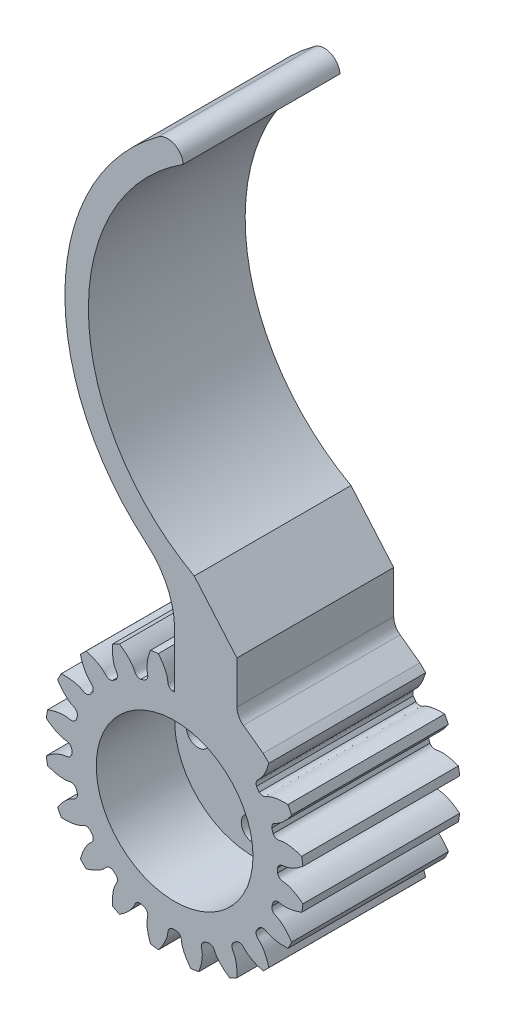
SolidWorks part; units mm, degrees
material "聚脂树脂"
ref_plane "前视基准面" through (0, 0, 0) normal (0, 0, 1) x (1, 0, 0)
ref_plane "上视基准面" through (0, 0, 0) normal (0, 1, 0) x (1, 0, 0)
ref_plane "右视基准面" through (0, 0, 0) normal (1, 0, 0) x (0, 0, -1)
other "Configuration Table"
sketch "草图1" plane through (0, 0, 0) normal (0, 0, 1) x (1, 0, 0)
  circle A0 centre (0, 0) radius 16.5
extrude "凸台-拉伸1" add sketch "草图1" along normal blind 20
ref_axis "基准轴1" through (0, 0, -1.5) along (0, 0, 1)
sketch "草图2" plane through (0, 0, 0) normal (0, 0, 1) x (1, 0, 0)
  line L0 (0, 0) -> (0, 16.5) construction
  circle A0 centre (0, 0) radius 16.5 construction
  arc A1 (0.29, 13.1218) -> (-0.29, 13.1218) centre (0, 0) ccw
  arc A2 (4.7717, 18.7474) -> (-4.7717, 18.7474) centre (0, 0) ccw
  spline S0 degree 3 poles (0.29, 13.1218) (0.9168, 13.3402) (0.8356, 13.7807) (0.9193, 14.205) (0.9283, 14.2463) (0.9395, 14.293) (0.9529, 14.3448) (0.969, 14.4018) (0.9878, 14.4638) (1.0095, 14.5309) (1.0345, 14.6028) (1.0629, 14.6795) (1.0948, 14.7608) (1.1305, 14.8467) (1.1702, 14.9371) (1.2141, 15.0317) (1.2623, 15.1305) (1.315, 15.2334) (1.3725, 15.3401) (1.4349, 15.4506) (1.5023, 15.5646) (1.575, 15.6821) (1.653, 15.8029) (1.7366, 15.9267) (1.826, 16.0534) (1.9211, 16.1829) (2.0223, 16.3149) (2.1296, 16.4493) (2.2432, 16.5859) (2.3632, 16.7244) (2.4897, 16.8646) (2.6229, 17.0065) (2.7628, 17.1496) (2.9095, 17.2939) (3.0632, 17.4391) (3.224, 17.585) (3.3918, 17.7313) (3.567, 17.8779) (3.7493, 18.0245) (3.9391, 18.1709) (4.1363, 18.3167) (4.4122, 18.5125) (4.6259, 18.6545) (4.7717, 18.7474) knots 0 0 0 0 0.165916 0.170906 0.176664 0.183189 0.190482 0.198542 0.207371 0.216967 0.22733 0.238462 0.250361 0.263027 0.276462 0.290664 0.305634 0.321371 0.337876 0.355149 0.37319 0.391998 0.411574 0.431917 0.453028 0.474907 0.497554 0.520968 0.54515 0.570099 0.595817 0.622302 0.649554 0.677575 0.706363 0.735918 0.766242 0.797333 0.829191 0.861818 0.895212 0.929373 1 1 1 1
  spline S1 degree 3 poles (-0.29, 13.1218) (-0.9168, 13.3402) (-0.8356, 13.7807) (-0.9193, 14.205) (-0.9283, 14.2463) (-0.9395, 14.293) (-0.9529, 14.3448) (-0.969, 14.4018) (-0.9878, 14.4638) (-1.0095, 14.5309) (-1.0345, 14.6028) (-1.0629, 14.6795) (-1.0948, 14.7608) (-1.1305, 14.8467) (-1.1702, 14.9371) (-1.2141, 15.0317) (-1.2623, 15.1305) (-1.315, 15.2334) (-1.3725, 15.3401) (-1.4349, 15.4506) (-1.5023, 15.5646) (-1.575, 15.6821) (-1.653, 15.8029) (-1.7366, 15.9267) (-1.826, 16.0534) (-1.9211, 16.1829) (-2.0223, 16.3149) (-2.1296, 16.4493) (-2.2432, 16.5859) (-2.3632, 16.7244) (-2.4897, 16.8646) (-2.6229, 17.0065) (-2.7628, 17.1496) (-2.9095, 17.2939) (-3.0632, 17.4391) (-3.224, 17.585) (-3.3918, 17.7313) (-3.567, 17.8779) (-3.7493, 18.0245) (-3.9391, 18.1709) (-4.1363, 18.3167) (-4.4122, 18.5125) (-4.6259, 18.6545) (-4.7717, 18.7474) knots 0 0 0 0 0.165916 0.170906 0.176664 0.183189 0.190482 0.198542 0.207371 0.216967 0.22733 0.238462 0.250361 0.263027 0.276462 0.290664 0.305634 0.321371 0.337876 0.355149 0.37319 0.391998 0.411574 0.431917 0.453028 0.474907 0.497554 0.520968 0.54515 0.570099 0.595817 0.622302 0.649554 0.677575 0.706363 0.735918 0.766242 0.797333 0.829191 0.861818 0.895212 0.929373 1 1 1 1
extrude "切除-拉伸1" cut sketch "草图2" along normal through all
pattern_circular "阵列(圆周)1" count 20 over 360 about axis through (0, 0, -1.5) along (0, 0, 1) of "切除-拉伸1"
sketch "草图3" plane through (0, 0, 0) normal (0, 0, 1) x (1, 0, 0)
  circle A0 centre (0, 0) radius 15 construction
  dimension "Dn" = 30
sketch "草图4" plane through (0, 0, 0) normal (0, 0, -1) x (-1, 0, 0)
  line L0 (0, 0) -> (67.6919, 0) construction
  line L1 (0, 13.125) -> (0, 76.7697) construction
  line L2 (-15, 0) -> (-15, 67.6903) construction
  line L3 (-7.9502, 14.4584) -> (-7.9502, 25)
  line L4 (0, 13.125) -> (0, 25.2067)
  line L5 (-2.1023, 76) -> (-1.1024, 72)
  line L6 (-7.9502, 14.4584) -> (-11.294, 12.029)
  circle A2 centre (-15, 50.026) radius 26 construction
  circle A3 centre (-15, 50.026) radius 29 construction
  arc A4 (-7.9502, 25) -> (-1.1024, 72) centre (-15, 50.026) ccw
  arc A5 (0, 25.2067) -> (-2.1023, 76) centre (-15, 50.026) ccw
  arc A6 (0.29, 13.1218) -> (-0.29, 13.1218) centre (0, 0) ccw construction
  arc A7 (-2.0665, 16.3701) -> (-3.0932, 16.2075) centre (0, 0) ccw construction
  arc A8 (-3.7791, 12.5692) -> (-4.3306, 12.39) centre (0, 0) ccw construction
  arc A9 (-7.024, 14.9303) -> (-7.9502, 14.4584) centre (0, 0) ccw construction
  arc A10 (0, 13.125) -> (-0.29, 13.1218) centre (0, 0) ccw
  arc A11 (-2.0665, 16.3701) -> (-3.0932, 16.2075) centre (0, 0) ccw
  arc A12 (-3.7791, 12.5692) -> (-4.3306, 12.39) centre (0, 0) ccw
  arc A13 (-7.024, 14.9303) -> (-7.9502, 14.4584) centre (0, 0) ccw
  arc A14 (-7.4782, 10.7862) -> (-7.9474, 10.4453) centre (0, 0) ccw construction
  arc A15 (-7.4782, 10.7862) -> (-7.9474, 10.4453) centre (0, 0) ccw
  spline S2 degree 3 poles (3856.7688, 1071.746) (-40.9447, -7.0022) (0.397, 7.533) (-0.9224, 14.2207) (-0.9359, 14.2793) (-0.9529, 14.3448) (-0.969, 14.4018) (-0.9951, 14.4881) (-1.0357, 14.6084) (-1.0961, 14.7664) (-1.1716, 14.9426) (-1.2638, 15.1361) (-1.3741, 15.3456) (-1.5041, 15.5702) (-1.6549, 15.8084) (-1.7965, 16.0133) (-1.9211, 16.1829) (-22.6396, 43.218) (-204.8238, -56.137) (3987.8439, 293.2807) knots -2.601051 -2.601051 -2.601051 -2.601051 0.165916 0.170906 0.183189 0.190482 0.198542 0.207371 0.22733 0.250361 0.276462 0.305634 0.337876 0.37319 0.411574 0.453028 0.474907 0.497554 14.365332 14.365332 14.365332 14.365332 only from (-0.29, 13.1218) to (-2.0665, 16.3701) construction
  spline S3 degree 3 poles (-3999.1929, -172.5161) (41.1045, 5.9931) (-2.7054, 7.0416) (-3.5171, 13.8097) (-3.5224, 13.8696) (-3.5265, 13.9372) (-3.5289, 13.9963) (-3.5307, 14.0865) (-3.5293, 14.2134) (-3.5206, 14.3824) (-3.5033, 14.5733) (-3.4754, 14.7858) (-3.4352, 15.0192) (-3.381, 15.2729) (-3.3111, 15.5461) (-3.2398, 15.7847) (-3.1737, 15.9845) (8.1764, 48.0988) (212.1463, 9.9046) (-3883.2936, -953.385) knots -2.108482 -2.108482 -2.108482 -2.108482 0.658484 0.663474 0.675757 0.68305 0.691111 0.699939 0.719899 0.742929 0.76903 0.798202 0.830445 0.865758 0.904142 0.945597 0.967475 0.990122 14.8579 14.8579 14.8579 14.8579 only from (-3.7791, 12.5692) to (-3.0932, 16.2075) construction
  spline S4 degree 3 poles (3336.8174, 2211.0982) (-36.7769, -19.3121) (-1.9503, 7.287) (-5.2717, 13.2396) (-5.3027, 13.2912) (-5.3391, 13.3482) (-5.3719, 13.3975) (-5.4235, 13.4715) (-5.4992, 13.5733) (-5.6055, 13.705) (-5.7318, 13.8492) (-5.8792, 14.0047) (-6.0489, 14.1699) (-6.2419, 14.3433) (-6.459, 14.5233) (-6.6569, 14.6744) (-6.8279, 14.7972) (-34.8866, 34.1067) (-177.4517, -116.6835) (3702.0362, 1511.238) knots -2.601051 -2.601051 -2.601051 -2.601051 0.165916 0.170906 0.183189 0.190482 0.198542 0.207371 0.22733 0.250361 0.276462 0.305634 0.337876 0.37319 0.411574 0.453028 0.474907 0.497554 14.365332 14.365332 14.365332 14.365332 only from (-4.3306, 12.39) to (-7.024, 14.9303) construction
  spline S5 degree 3 poles (-0.29, 13.1218) (-0.9168, 13.3402) (-0.8356, 13.7807) (-0.9224, 14.2207) (-0.9359, 14.2793) (-0.9529, 14.3448) (-0.969, 14.4018) (-0.9951, 14.4881) (-1.0357, 14.6084) (-1.0961, 14.7664) (-1.1716, 14.9426) (-1.2638, 15.1361) (-1.3741, 15.3456) (-1.5041, 15.5702) (-1.6549, 15.8084) (-1.828, 16.0589) (-1.969, 16.2466) (-2.0515, 16.3512) (-2.0665, 16.3701) knots 0 0 0 0 0.165916 0.170906 0.183189 0.190482 0.198542 0.207371 0.22733 0.250361 0.276462 0.305634 0.337876 0.37319 0.411574 0.453028 0.497554 0.507432 0.507432 0.507432 0.507432
  spline S6 degree 3 poles (-3.7791, 12.5692) (-3.2504, 12.9706) (-3.4637, 13.3644) (-3.5171, 13.8097) (-3.5224, 13.8696) (-3.5265, 13.9372) (-3.5289, 13.9963) (-3.5307, 14.0865) (-3.5293, 14.2134) (-3.5206, 14.3824) (-3.5033, 14.5733) (-3.4754, 14.7858) (-3.4352, 15.0192) (-3.381, 15.2729) (-3.3111, 15.5461) (-3.224, 15.8378) (-3.1479, 16.0599) (-3.1017, 16.1848) (-3.0932, 16.2075) knots 0.492568 0.492568 0.492568 0.492568 0.658484 0.663474 0.675757 0.68305 0.691111 0.699939 0.719899 0.742929 0.76903 0.798202 0.830445 0.865758 0.904142 0.945597 0.990122 1 1 1 1
  spline S7 degree 3 poles (-4.3306, 12.39) (-4.9943, 12.404) (-5.0532, 12.848) (-5.2717, 13.2396) (-5.3027, 13.2912) (-5.3391, 13.3482) (-5.3719, 13.3975) (-5.4235, 13.4715) (-5.4992, 13.5733) (-5.6055, 13.705) (-5.7318, 13.8492) (-5.8792, 14.0047) (-6.0489, 14.1699) (-6.2419, 14.3433) (-6.459, 14.5233) (-6.701, 14.7081) (-6.8931, 14.843) (-7.0039, 14.9169) (-7.024, 14.9303) knots 0 0 0 0 0.165916 0.170906 0.183189 0.190482 0.198542 0.207371 0.22733 0.250361 0.276462 0.305634 0.337876 0.37319 0.411574 0.453028 0.497554 0.507432 0.507432 0.507432 0.507432
  spline S8 degree 3 poles (-3750.148, -1399.8911) (37.2407, 18.4018) (-4.7489, 5.861) (-7.6124, 12.047) (-7.636, 12.1023) (-7.6607, 12.1653) (-7.6812, 12.2208) (-7.7108, 12.3061) (-7.7487, 12.4272) (-7.7927, 12.5905) (-7.8352, 12.7775) (-7.8743, 12.9882) (-7.9082, 13.2226) (-7.9351, 13.4806) (-7.9531, 13.762) (-7.959, 14.011) (-7.9578, 14.2215) (-7.0871, 48.2713) (198.7024, 74.9766) (-3398.6195, -2106.7268) knots -2.108482 -2.108482 -2.108482 -2.108482 0.658484 0.663474 0.675757 0.68305 0.691111 0.699939 0.719899 0.742929 0.76903 0.798202 0.830445 0.865758 0.904142 0.945597 0.967475 0.990122 14.8579 14.8579 14.8579 14.8579 only from (-7.4782, 10.7862) to (-7.9502, 14.4584) construction
  spline S9 degree 3 poles (2490.235, 3134.0126) (-29.0091, -29.7316) (-4.1066, 6.3277) (-9.105, 10.9626) (-9.1503, 11.0021) (-9.2026, 11.0451) (-9.2491, 11.0817) (-9.321, 11.1362) (-9.4245, 11.2097) (-9.5662, 11.302) (-9.7309, 11.4002) (-9.9192, 11.5025) (-10.1316, 11.6072) (-10.3687, 11.7125) (-10.6308, 11.8165) (-10.8658, 11.8991) (-11.0663, 11.963) (-43.7187, 21.6569) (-132.7094, -165.8082) (3053.8474, 2581.2649) knots -2.601051 -2.601051 -2.601051 -2.601051 0.165916 0.170906 0.183189 0.190482 0.198542 0.207371 0.22733 0.250361 0.276462 0.305634 0.337876 0.37319 0.411574 0.453028 0.474907 0.497554 14.365332 14.365332 14.365332 14.365332 only from (-7.9474, 10.4453) to (-11.294, 12.029) construction
  spline S10 degree 3 poles (-7.4782, 10.7862) (-7.0995, 11.3313) (-7.424, 11.64) (-7.6124, 12.047) (-7.636, 12.1023) (-7.6607, 12.1653) (-7.6812, 12.2208) (-7.7108, 12.3061) (-7.7487, 12.4272) (-7.7927, 12.5905) (-7.8352, 12.7775) (-7.8743, 12.9882) (-7.9082, 13.2226) (-7.9351, 13.4806) (-7.9531, 13.762) (-7.9603, 14.0664) (-7.9566, 14.3011) (-7.9513, 14.4342) (-7.9502, 14.4584) knots 0.492568 0.492568 0.492568 0.492568 0.658484 0.663474 0.675757 0.68305 0.691111 0.699939 0.719899 0.742929 0.76903 0.798202 0.830445 0.865758 0.904142 0.945597 0.990122 1 1 1 1
  spline S11 degree 3 poles (-7.9474, 10.4453) (-8.5829, 10.2536) (-8.7761, 10.6576) (-9.105, 10.9626) (-9.1503, 11.0021) (-9.2026, 11.0451) (-9.2491, 11.0817) (-9.321, 11.1362) (-9.4245, 11.2097) (-9.5662, 11.302) (-9.7309, 11.4002) (-9.9192, 11.5025) (-10.1316, 11.6072) (-10.3687, 11.7125) (-10.6308, 11.8165) (-10.9181, 11.9175) (-11.1425, 11.9864) (-11.2707, 12.0225) (-11.294, 12.029) knots 0 0 0 0 0.165916 0.170906 0.183189 0.190482 0.198542 0.207371 0.22733 0.250361 0.276462 0.305634 0.337876 0.37319 0.411574 0.453028 0.497554 0.507432 0.507432 0.507432 0.507432
  dimension "D7" = 47
  dimension "D4" = 52
  dimension "D5" = 58
  dimension "D1" = 15
  dimension "D2" = 25
  dimension "D6" = 4
extrude "凸台-拉伸2" add sketch "草图4" against normal blind 20 contours S7 A12 S6 A11 S5 A10 L4 A5 L5 A4 L3 A13 | S11 A15 S10 L6 region at (8.8549, 12.1877, 0) region at (7.2773, 19.7292, 0)
fillet "圆角1" radius 10 1 edges at (0, 25.2067, 10)
fillet "圆角2" radius 2 2 edges at (2.1023, 76, 10) (7.9502, 14.4584, 10)
sketch "草图5" plane through (0, 0, 0) normal (0, 0, -1) x (-1, 0, 0)
  line L0 (0, 0) -> (47.9973, 0) construction
  line L1 (0, 0) -> (0, 54.3289) construction
sketch "草图7" plane through (0, 0, 20) normal (0, 0, 1) x (1, 0, 0)
  line L0 (0, 0) -> (42.9933, 0) construction
  line L1 (0, 0) -> (0, 51.6895) construction
  circle A0 centre (0, 0) radius 10
  dimension "D1" = 20
extrude "切除-拉伸2" cut sketch "草图7" against normal blind 10
sketch "草图8" plane through (0, 0, 10) normal (0, 0, 1) x (1, 0, 0)
  line L0 (0, 0) -> (25.4464, 0) construction
  line L1 (0, 0) -> (0, 31.9913) construction
  circle A0 centre (0, 0) radius 3.5
  circle A1 centre (0, 7) radius 1.5
  circle A2 centre (7, 0) radius 1.5
  circle A3 centre (0, -7) radius 1.5
  circle A4 centre (-7, 0) radius 1.5
  dimension "D1" = 3
  dimension "D2" = 7
  dimension "D4" = 3
  dimension "D3" = 7
  dimension "D5" = 7
extrude "切除-拉伸3" cut sketch "草图8" against normal blind 10
chamfer "倒角1" distance 5 angle 45 1 edges at (7.9502, 25, 10) first distance on face at (7.9502, 20.2387, 10)
sketch "草图9" plane through (0, 0, 20) normal (0, 0, -1) x (-1, 0, 0)
  line L0 (-2.5042, 27.2257) -> (-7.9502, 20.8839)
  line L1 (-7.9502, 20.8839) -> (0, 20.0927)
  arc A0 (3.5897, 27.7679) -> (0, 20.0927) centre (10, 20.0927) ccw construction
  arc A1 (3.5897, 27.7679) -> (2.0694, 73.4703) centre (-15, 50.026) ccw construction
  arc A2 (-2.5042, 27.2257) -> (-1.1024, 72) centre (-15, 50.026) ccw construction
  arc A3 (2.0694, 73.4703) -> (-1.1024, 72) centre (0.8922, 71.8534) ccw construction
  arc A4 (3.5897, 27.7679) -> (0, 20.0927) centre (10, 20.0927) ccw
  arc A5 (3.5897, 27.7679) -> (2.0694, 73.4703) centre (-15, 50.026) ccw
  arc A6 (-2.5042, 27.2257) -> (-1.1024, 72) centre (-15, 50.026) ccw
  arc A7 (2.0694, 73.4703) -> (-1.1024, 72) centre (0.8922, 71.8534) ccw
extrude "凸台-拉伸3" add sketch "草图9" along normal blind 10
